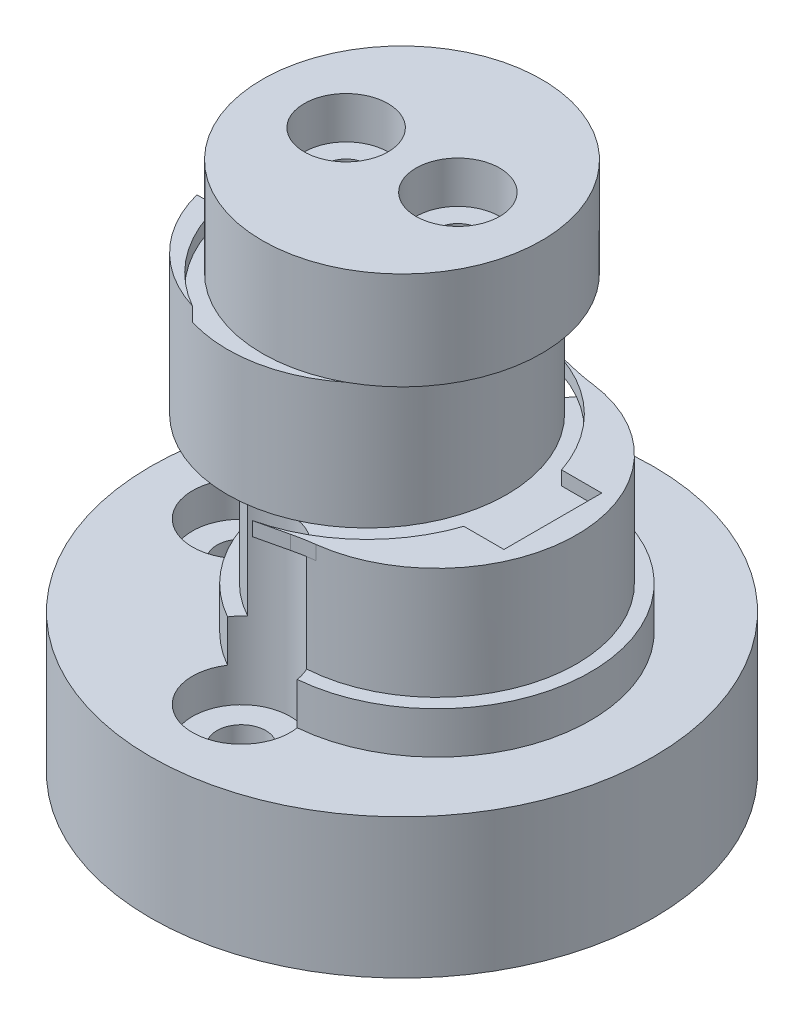
SolidWorks part; units mm, degrees
note: The reader was unsure of these and kept them because the rebuilt part matched: shared geometry of "Sketch15<2>".
material "PET"
ref_plane "Front Plane" through (0, 0, 0) normal (0, 0, 1) x (1, 0, 0)
ref_plane "Top Plane" through (0, 0, 0) normal (0, 1, 0) x (1, 0, 0)
ref_plane "Right Plane" through (0, 0, 0) normal (1, 0, 0) x (0, 0, -1)
sketch "Sketch2" plane through (0, 0, 0) normal (0, -1, 0) x (1, 0, 0)
  circle A0 centre (0, 0) radius 18
  dimension "D1" = 36
extrude "Boss-Extrude1" add sketch "Sketch2" against normal blind 10
sketch "Sketch3" plane through (0, 10, 0) normal (0, 1, 0) x (1, 0, 0)
  circle A0 centre (2.5, 0) radius 10
  dimension "D1" = 20
  dimension "D2" = 2.5
extrude "Boss-Extrude2" add sketch "Sketch3" along normal blind 10
sketch "Sketch4" plane through (0, 20, 0) normal (0, 1, 0) x (1, 0, 0)
  circle A0 centre (-2.5, 0) radius 10
  dimension "D1" = 20
  dimension "D2" = 2.5
extrude "Boss-Extrude3" add sketch "Sketch4" along normal blind 10
sketch "Sketch5" plane through (0, 30, 0) normal (0, 1, 0) x (1, 0, 0)
  circle A0 centre (0, 0) radius 10
  dimension "D1" = 20
extrude "Boss-Extrude4" add sketch "Sketch5" along normal blind 8
sketch "Sketch7" plane through (0, 10, 0) normal (0, 1, 0) x (1, 0, 0)
  circle A1 centre (2.5, 0) radius 11
  circle A2 centre (2.5, 0) radius 10
  circle A3 centre (2.5, 0) radius 10
  dimension "D1" = 0
  dimension "D2" = 1
extrude "Boss-Extrude5" add sketch "Sketch7" along normal blind 3
sketch "Sketch8" plane through (0, 20, 0) normal (0, 1, 0) x (1, 0, 0)
  circle A2 centre (-2.5, 0) radius 10
  circle A3 centre (-2.5, 0) radius 11
  dimension "D1" = 1
extrude "Boss-Extrude6" add sketch "Sketch8" along normal blind 1
sketch "Sketch9" plane through (0, 30, 0) normal (0, 1, 0) x (1, 0, 0)
  circle A1 centre (0, 0) radius 2
  circle A2 centre (0, 0) radius 11
  circle A3 centre (0, 0) radius 11
  dimension "D1" = 1
extrude "Boss-Extrude7" add sketch "Sketch9" along normal blind 1
sketch "Sketch11" plane through (0, 38, 0) normal (0, 1, 0) x (1, 0, 0)
  line L0 (0, 0) -> (0, 9.3141) construction
  circle A5 centre (4, 0) radius 1.5
  circle A6 centre (-4, 0) radius 1.5
  dimension "D1" = 3
  dimension "D2" = 4
extrude "Cut-Extrude4" cut sketch "Sketch11" against normal blind 35
sketch "Sketch12" plane through (0, 0, 0) normal (0, -1, 0) x (-1, 0, 0)
  circle A0 centre (0, 0) radius 14.5
extrude "Cut-Extrude5" cut sketch "Sketch12" against normal blind 5.5
sketch "Sketch14" plane through (0, 10, 0) normal (0, 1, 0) x (1, 0, 0)
  line L0 (0, -11.5) -> (0, 11.5) construction
  circle A0 centre (-11.5, 0) radius 1.75
  circle A1 centre (0, -11.5) radius 1.75
  circle A2 centre (0, 11.5) radius 1.75
  point P4 (0, 0)
  dimension "D1" = 3.5
  dimension "D2" = 3.5
  dimension "D3" = 3.5
  dimension "D4" = 23
  dimension "D5" = 0
  dimension "D6" = 11.5
extrude "Cut-Extrude6" cut sketch "Sketch14" against normal blind 4.5
sketch "Sketch15" plane through (0, 10, 0) normal (0, 1, 0) x (1, 0, 0)
  circle A0 centre (-11.5, 0) radius 3.5
  circle A1 centre (0, -11.5) radius 3.5
  circle A2 centre (0, 11.5) radius 3.5
  dimension "D1" = 7
  dimension "D2" = 7
  dimension "D3" = 7
extrude "Cut-Extrude7" cut sketch "Sketch15" along normal up to surface (10 mm away) up to face at (10.5, 20, 0)
extrude "Cut-Extrude8" cut sketch "Sketch15<2>" against normal blind 2.5
sketch "Sketch15<2>" plane through (0, 10, 0) normal (0, 1, 0) x (1, 0, 0) same geometry as "Sketch15"
sketch "Sketch16" plane through (0, 20, 0) normal (0, 1, 0) x (1, 0, 0)
  line L0 (0, 0) -> (21.518, 0) construction
  line L1 (3.1521, -9.9787) -> (-0.0071, -10.7138)
  line L2 (3.1521, 9.9787) -> (-0.0071, 10.7138)
  arc A0 (-0.0071, -10.7138) -> (2.9208, -9.5716) centre (-2.5, 0) ccw
  arc A6 (2.9208, 9.5716) -> (2.9208, -9.5716) centre (-2.5, 0) ccw
  arc A7 (2.9208, 9.5716) -> (-0.0071, 10.7138) centre (-2.5, 0) ccw
  arc A8 (2.9208, -9.5716) -> (2.9208, 9.5716) centre (-2.5, 0) ccw
  arc A9 (3.1521, -9.9787) -> (2.9208, -9.5716) centre (0, -11.5) ccw
  arc A10 (3.1521, -9.9787) -> (3.1521, 9.9787) centre (2.5, 0) ccw
  arc A11 (2.9208, 9.5716) -> (3.1521, 9.9787) centre (0, 11.5) ccw
  arc A12 (2.9208, -9.5716) -> (2.9208, 9.5716) centre (-2.5, 0) ccw
  arc A14 (3.1521, -9.9787) -> (3.1521, 9.9787) centre (2.5, 0) ccw
  dimension "D1" = 0
  dimension "D2" = 0
extrude "Boss-Extrude8" add sketch "Sketch16" along normal blind 1
sketch "Sketch18" plane through (0, 5.5, 0) normal (0, -1, 0) x (1, 0, 0)
  line L0 (0, 0) -> (0, 5.3455) construction
  line L13 (-0.7091, 0) -> (-2.3546, 2.85)
  line L14 (-2.3546, 2.85) -> (-5.6454, 2.85)
  line L15 (-5.6454, 2.85) -> (-7.2909, 0)
  line L16 (-7.2909, 0) -> (-5.6454, -2.85)
  line L17 (-5.6454, -2.85) -> (-2.3546, -2.85)
  line L18 (-2.3546, -2.85) -> (-0.7091, 0)
  line L19 (2.3546, -2.85) -> (0.7091, 0)
  line L20 (5.6454, -2.85) -> (2.3546, -2.85)
  line L21 (7.2909, 0) -> (5.6454, -2.85)
  line L22 (5.6454, 2.85) -> (7.2909, 0)
  line L23 (2.3546, 2.85) -> (5.6454, 2.85)
  line L24 (0.7091, 0) -> (2.3546, 2.85)
  circle A0 centre (-4, 0) radius 2.85 construction
  dimension "D1" = 5.7
extrude "Cut-Extrude11" cut sketch "Sketch18" against normal blind 4
sketch "Sketch19" plane through (0, 38, 0) normal (0, 1, 0) x (1, 0, 0)
  line L0 (0, 0) -> (0, 8.5021) construction
  circle A2 centre (4, 0) radius 3
  circle A3 centre (-4, 0) radius 3
  dimension "D1" = 6
extrude "Cut-Extrude12" cut sketch "Sketch19" against normal blind 3
fillet "Fillet1" radius 15 2 edges at (3.1521, 20.5, -9.9787) (3.1521, 20.5, 9.9787)
ref_plane "Plane2" through (0, 30, 0) normal (0, 1, 0) x (1, 0, 0)
ref_plane "Plane3" through (0, 20, 0) normal (0, 1, 0) x (1, 0, 0)
sketch "Sketch20" plane through (0, 30, 0) normal (0, 1, 0) x (1, 0, 0)
  line L0 (-6.5, 9.1652) -> (-4.4, 10.0817)
  line L1 (0, 0) -> (-9.8107, 0) construction
  line L2 (-6.5, -9.1652) -> (-4.4, -10.0817)
  circle A9 centre (0, 0) radius 11
  arc A10 (-4.4, 10.0817) -> (-4.4, -10.0817) centre (0, 0) ccw
  circle A12 centre (-2.5, 0) radius 10
  circle A13 centre (-2.5, 0) radius 10
  circle M7 centre (-2.5, 0) radius 10
  dimension "D1" = 0
  dimension "D2" = 0
extrude "Boss-Extrude9" add sketch "Sketch20" along normal blind 1 contours A10 M7
sketch "Sketch21" plane through (0, 21, 0) normal (0, 1, 0) x (1, 0, 0)
  line L2 (0, 0) -> (10.518, 0) construction
  line L4 (10.8, -3.5) -> (7.8, -3.5)
  line L5 (10.8, -3.5) -> (10.8, 3.5)
  line L6 (10.8, 3.5) -> (7.8, 3.5)
  line L7 (7.8, -3.5) -> (7.8, 3.5)
  line L8 (10.8, -3.5) -> (7.8, 3.5) construction
  line L9 (10.8, 3.5) -> (7.8, -3.5) construction
  circle A6 centre (-2.5, 0) radius 11
  point P4 (9.3, 0)
  arc M4 (-0.0071, 10.7138) -> (-0.0071, -10.7138) centre (-2.5, 0) ccw
  circle M10 centre (-2.5, 0) radius 10
  dimension "D3" = 2.5
  dimension "D4" = 22
  dimension "D1" = 3
  dimension "D2" = 7
  dimension "D5" = 11.8
extrude "Cut-Extrude14" cut sketch "Sketch21" against normal blind 1 contours A6 L4 L7 L6 M4 M10 | M10 | A6 L4 L5 L6 | L4 A6 L6 L7
sketch "Sketch23" plane through (0, 31, 0) normal (0, 1, 0) x (1, 0, 0)
  line L0 (0, 0) -> (-14.1712, 0) construction
  line L2 (-12.7486, -2.5) -> (-9.2514, -2.5)
  line L3 (-12.7486, -2.5) -> (-12.7486, 2.5)
  line L4 (-12.7486, 2.5) -> (-9.2514, 2.5)
  line L5 (-9.2514, -2.5) -> (-9.2514, 2.5)
  line L6 (-12.7486, -2.5) -> (-9.2514, 2.5) construction
  line L7 (-12.7486, 2.5) -> (-9.2514, -2.5) construction
  circle A0 centre (0, 0) radius 11
  point P3 (-11, 0)
  circle M2 centre (0, 0) radius 10
  arc M3 (-5.45, -9.555) -> (-5.45, 9.555) centre (0, 0) ccw
  arc M14 (-5.45, 9.555) -> (-5.45, -9.555) centre (-2.5, 0) ccw
  dimension "D1" = 22
  dimension "D2" = 5
extrude "Cut-Extrude18" cut sketch "Sketch23" against normal blind 1 contours L4 L3 L2 M14 | A0 L4 L2 M14 | L4 A0 L2 M2 | L2 L5 L4 M2 | A0 L4 L2 M3 M2
other "Save Bodies1"
